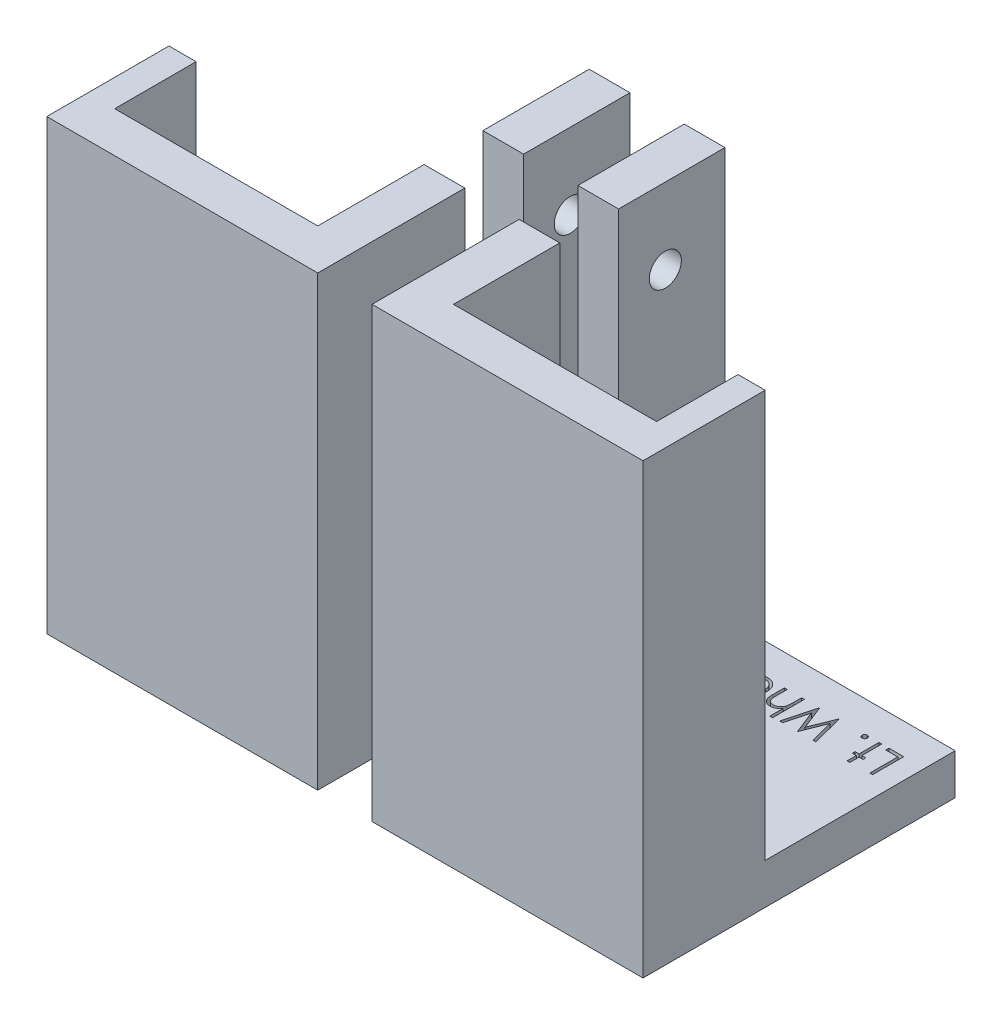
SolidWorks part; units mm, degrees
ref_plane "Front Plane" through (0, 0, 0) normal (0, 0, 1) x (1, 0, 0)
ref_plane "Top Plane" through (0, 0, 0) normal (0, 1, 0) x (1, 0, 0)
ref_plane "Right Plane" through (0, 0, 0) normal (1, 0, 0) x (0, 0, -1)
sketch "Sketch2" plane through (0, 0, 0) normal (0, 1, 0) x (1, 0, 0)
  line L10 (-13.31, -12.7) -> (-13.31, 16.51)
  line L15 (-13.31, 16.51) -> (12.04, 16.51)
  line L16 (12.04, 16.51) -> (12.04, 5.08)
  line L18 (12.04, 5.08) -> (9.5, 5.08)
  line L19 (9.5, 5.08) -> (9.5, 12.7)
  line L20 (9.5, 12.7) -> (-9.5, 12.7)
  line L21 (-9.5, 12.7) -> (-9.5, -12.7)
  line L23 (-9.5, -12.7) -> (-13.31, -12.7)
  point P6 (0, 12.7)
  point P12 (-9.5, 0)
  dimension "D1" = 25.4
  dimension "D2" = 19
  dimension "D3" = 3.81
  dimension "D4" = 3.81
  dimension "D5" = 5.08
  dimension "D6" = 2.54
extrude "Boss-Extrude2" add sketch "Sketch2" along normal blind 38.1
sketch "Sketch1" plane through (0, 0, 0) normal (0, 1, 0) x (1, 0, 0)
  line L1 (-13.31, -12.7) -> (12.04, -12.7)
  line L2 (-13.31, -12.7) -> (-13.31, 16.51)
  line L3 (-13.31, 16.51) -> (12.04, 16.51)
  line L4 (12.04, -12.7) -> (12.04, 16.51)
  point P0 (0, 0)
extrude "Boss-Extrude3" add sketch "Sketch1" against normal blind 3.81
sketch "Sketch3" plane through (0, 0, 0) normal (0, 1, 0) x (1, 0, 0)
  line L1 (-1.5, -3.81) -> (1.5, -3.81)
  line L2 (-1.5, -3.81) -> (-1.5, 3.81)
  line L3 (-1.5, 3.81) -> (1.5, 3.81)
  line L4 (1.5, -3.81) -> (1.5, 3.81)
  point P4 (0, -3.81)
  point P6 (-1.5, 0)
  dimension "D1" = 7.62
  dimension "D2" = 3
extrude "Cut-Extrude1" cut sketch "Sketch3" against normal through all
sketch "Sketch4" plane through (-9.5, 0, 0) normal (1, 0, 0) x (0, 0, -1)
  line L0 (-12.7, 38.1) -> (12.7, 38.1) construction
  line L1 (-2.75, 38.1) -> (2.75, 38.1)
  line L2 (-2.75, 38.1) -> (-2.75, 8)
  line L3 (-2.75, 8) -> (2.75, 8)
  line L4 (2.75, 38.1) -> (2.75, 8)
  line L5 (-12.7, 0) -> (12.7, 0) construction
  line L6 (-12.7, 38.1) -> (12.7, 38.1) construction
  point P10 (0, 38.1)
  point P11 (0, 38.1)
  dimension "D1" = 8
  dimension "D2" = 5.5
extrude "Cut-Extrude2" cut sketch "Sketch4" against normal through all
sketch "Sketch5" plane through (-9.5, 0, 0) normal (1, 0, 0) x (0, 0, -1)
  line L0 (12.7, 38.1) -> (12.7, 0) construction
  line L1 (-12.7, 0) -> (12.7, 0) construction
  circle A0 centre (-7.118, 31) radius 1.5
  circle A1 centre (9.9, 31) radius 1.5
  dimension "D3" = 3
  dimension "D1" = 2.8
  dimension "D2" = 17.018
  dimension "D4" = 31
extrude "Cut-Extrude3" cut sketch "Sketch5" against normal through all
sketch "Sketch6" plane through (0, 0, 12.7) normal (0, 0, 1) x (1, 0, 0)
  line L1 (-9.5, 38.1) -> (-9.5, 0) construction
  line L4 (-13.31, 38.1) -> (-13.31, -3.81) construction
  line L5 (12.04, -3.81) -> (12.04, 0) construction
  line L7 (-13.31, 38.1) -> (-9.5, 38.1) construction
  circle A0 centre (-11.405, 19.05) radius 1.45
  circle A1 centre (-3.81, -1.905) radius 1.45
  point P12 (-9.5, 19.05)
  point P18 (12.04, -1.905)
  point P20 (-11.405, 38.1)
  dimension "D1" = 2.9
  dimension "D2" = 9.5
extrude "Cut-Extrude4" cut sketch "Sketch6" against normal offset from surface (22.054 mm away) 6.604 up to face at (-11.405, 23.05, -2.75) offset beyond the face yes
fillet "Fillet1" radius 4 1 edges at (0, 0, -12.7)
mirror "Mirror1" about plane through (0, 0, 0) normal (0, 0, 1) of bodies 106
delete or keep bodies "Body-Delete/Keep 1" type delete bodies bodies 106
ref_plane "Plane1" through (-15.85, 0, 0) normal (-1, 0, 0) x (0, 0, 1)
mirror "Mirror3" about plane through (-15.85, 0, 0) normal (-1, 0, 0) of bodies 116 117
sketch "Sketch7" plane through (0, 0, 0) normal (0, 1, 0) x (1, 0, 0)
  line L0 (10.4888, 9.8091) -> (-6.7319, 9.8091) construction
  text T0 "Lt. Wheel" font "Century Gothic" height in points 11
  point P3 (10.6388, 9.9237)
  point P4 (11.6693, 9.8999)
  point P5 (10.4888, 9.8091)
extrude "Cut-Extrude5" cut sketch "Sketch7" against normal blind 1.27
sketch "Sketch8" plane through (0, 0, 0) normal (0, 1, 0) x (1, 0, 0)
  line L0 (-42.5237, 9.9556) -> (-22.2037, 9.9556) construction
  text T0 "Rt. Wheel" font "Century Gothic" height in points 11
  point P3 (-42.5237, 10.0751)
  point P4 (-23.0386, 9.9556)
  point P5 (-32.3637, 9.9556)
  dimension "D1" = 20.32
extrude "Cut-Extrude6" cut sketch "Sketch8" against normal blind 1.27
equation "\".30.83in\"=0.83"
